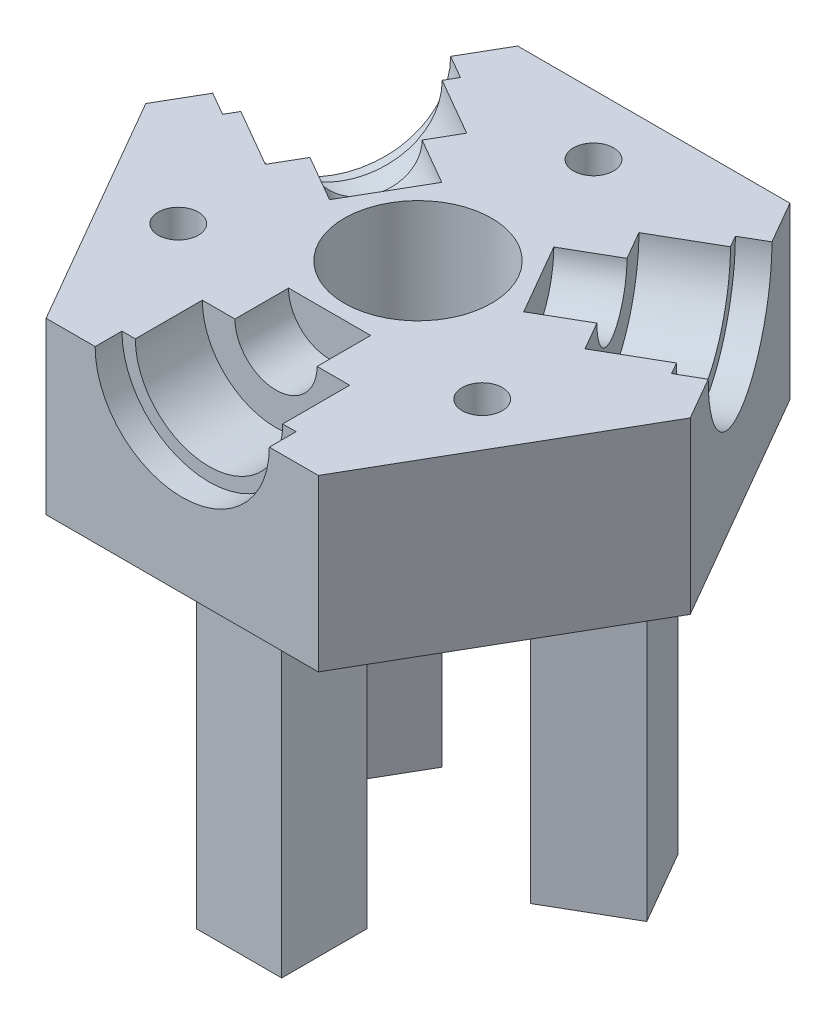
SolidWorks part; units mm, degrees
ref_plane "Front Plane" through (0, 0, 0) normal (0, 0, 1) x (1, 0, 0)
ref_plane "Top Plane" through (0, 0, 0) normal (0, 1, 0) x (1, 0, 0)
ref_plane "Right Plane" through (0, 0, 0) normal (1, 0, 0) x (0, 0, -1)
sketch "Sketch1" plane through (0, 0, 0) normal (0, 1, 0) x (1, 0, 0)
  line L1 (10.16, -17.5976) -> (20.32, 0)
  line L2 (20.32, 0) -> (10.16, 17.5976)
  line L3 (10.16, 17.5976) -> (-10.16, 17.5976)
  line L4 (-10.16, 17.5976) -> (-20.32, 0)
  line L5 (-20.32, 0) -> (-10.16, -17.5976)
  line L6 (-10.16, -17.5976) -> (10.16, -17.5976)
  circle A0 centre (0, 0) radius 17.5976 construction
  dimension "D1" = 20.32
extrude "Boss-Extrude1" add sketch "Sketch1" along normal blind 12.7 contours L4 L5 L6 L1 L2 L3
sketch "Sketch2" plane through (0, 0, 0) normal (0, -1, 0) x (1, 0, 0)
  circle A0 centre (0, 0) radius 5.5
  circle A1 centre (0, 0) radius 8.5
  dimension "D1" = 11
  dimension "D2" = 3
extrude "Boss-Extrude2" add sketch "Sketch2" along normal blind 3.5
sketch "Sketch4" plane through (0, 0, 0) normal (0, -1, 0) x (1, 0, 0)
  line L0 (13.1489, -3.9254) -> (7.6497, -0.7504)
  line L1 (-3.175, 13.35) -> (3.175, 13.35)
  line L2 (-3.175, 13.35) -> (-3.175, 7)
  line L3 (-3.175, 7) -> (3.175, 7)
  line L4 (3.175, 13.35) -> (3.175, 7)
  line L5 (-3.175, 13.35) -> (3.175, 7) construction
  line L6 (-3.175, 7) -> (3.175, 13.35) construction
  line L7 (13.1489, -3.9254) -> (9.9739, -9.4246)
  line L8 (9.9739, -9.4246) -> (4.4747, -6.2496)
  line L9 (7.6497, -0.7504) -> (4.4747, -6.2496)
  line L10 (-9.9739, -9.4246) -> (-4.4747, -6.2496)
  line L11 (-9.9739, -9.4246) -> (-13.1489, -3.9254)
  line L12 (-13.1489, -3.9254) -> (-7.6497, -0.7504)
  line L13 (-4.4747, -6.2496) -> (-7.6497, -0.7504)
  circle A1 centre (0, 0) radius 5.5 construction
  circle A2 centre (0, 0) radius 5.5 construction
  point P0 (0, 10.175)
  point P18 (0, 0)
  dimension "D1" = 6.35
  dimension "D2" = 1.5
  dimension "D4" = 1.5
  dimension "D5" = 1.5
  dimension "D3" = 3
extrude "Boss-Extrude4" add sketch "Sketch4" along normal blind 25.4
sketch "Sketch5" plane through (0, 12.7, 0) normal (0, 1, 0) x (1, 0, 0)
  line L14 (0, -17.5976) -> (0, -6.5976)
  line L15 (-10.16, -17.5976) -> (10.16, -17.5976) construction
  line L16 (0, -6.5976) -> (-3.0653, -6.5976)
  line L17 (-3.0653, -6.5976) -> (-3.0653, -10.5976)
  line L18 (-3.0653, -10.5976) -> (-5.5, -10.5976)
  line L19 (-5.5, -10.5976) -> (-5.5, -15.5976)
  line L20 (-5.5, -15.5976) -> (-6.5, -15.5976)
  line L21 (-6.5, -15.5976) -> (-6.5, -17.5976)
  line L22 (-6.5, -17.5976) -> (0, -17.5976)
  dimension "D1" = 6.5
  dimension "D2" = 5.5
  dimension "D3" = 2
  dimension "D4" = 5
  dimension "D5" = 4
  dimension "D6" = 3.0653
revolve "Cut-Revolve1" cut sketch "Sketch5" angle 360 about L14
pattern_circular "CirPattern1" count 3 over 360 about axis through (0, -3.5, 0) along (0, 1, 0) of "Cut-Revolve1" reverse direction yes
sketch "Sketch6" plane through (0, 12.7, 0) normal (0, 1, 0) x (1, 0, 0)
  circle A0 centre (0, 0) radius 5.5
  dimension "D1" = 11
extrude "Cut-Extrude1" cut sketch "Sketch6" against normal through all
sketch "Sketch7" plane through (0, 12.7, 0) normal (0, 1, 0) x (1, 0, 0)
  line L0 (10.16, 17.5976) -> (-10.16, 17.5976) construction
  line L1 (-20.32, 0) -> (-10.16, -17.5976) construction
  line L2 (10.16, -17.5976) -> (20.32, 0) construction
  circle A0 centre (0, 13.0976) radius 1.5
  circle A1 centre (11.3429, -6.5488) radius 1.5
  circle A2 centre (-11.3429, -6.5488) radius 1.5
  point P11 (0, 0)
  dimension "D1" = 3
  dimension "D2" = 3
  dimension "D4" = 3
  dimension "D5" = 3
  dimension "D3" = 3
extrude "Cut-Extrude2" cut sketch "Sketch7" against normal up to surface (12.7 mm away) up to face at (0, 0, 0)
